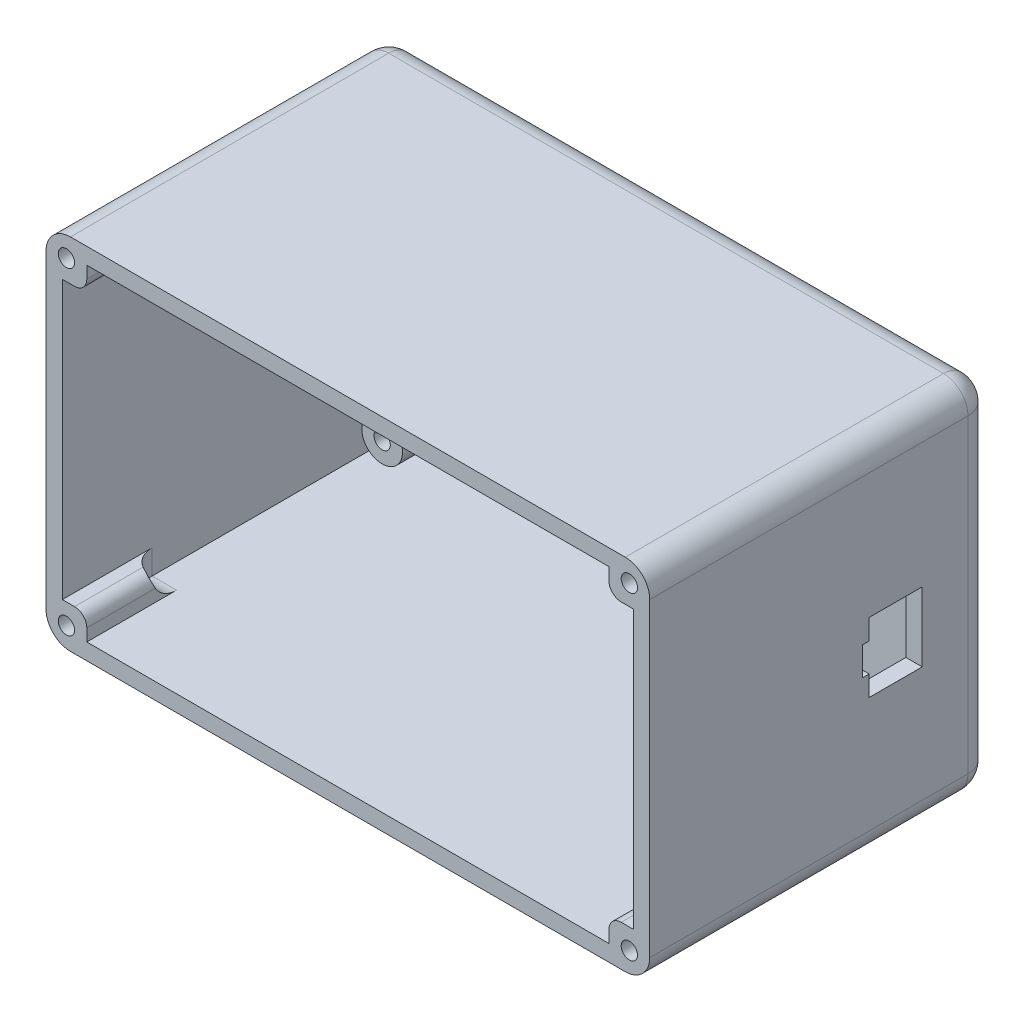
SolidWorks part; units mm, degrees
ref_plane "Front" through (0, 0, 0) normal (0, 0, 1) x (1, 0, 0)
ref_plane "Top" through (0, 0, 0) normal (0, 1, 0) x (1, 0, 0)
ref_plane "Right" through (0, 0, 0) normal (1, 0, 0) x (0, 0, -1)
sketch "Çizim1" plane through (0, 0, 0) normal (0, 0, 1) x (1, 0, 0)
  line L1 (-35, 20) -> (35, 20)
  line L2 (-35, 20) -> (-35, -20)
  line L3 (-35, -20) -> (35, -20)
  line L4 (35, 20) -> (35, -20)
  line L5 (-35, 20) -> (35, -20) construction
  line L6 (-35, -20) -> (35, 20) construction
  point P0 (0, 0)
  dimension "D1" = 70
  dimension "D2" = 40
extrude "Yükseklik-Ekstrüzyon1" add sketch "Çizim1" along normal blind 40
shell "İç Boşaltma2" thickness 2 removed face at (0, 0, 40) outward yes
sketch "Çizim2" plane through (0, 0, 0) normal (0, 0, 1) x (1, 0, 0)
  line L1 (-30.8, 15.5) -> (30.8, 15.5) construction
  line L2 (-30.8, 15.5) -> (-30.8, -15.5) construction
  line L3 (-30.8, -15.5) -> (30.8, -15.5) construction
  line L4 (30.8, 15.5) -> (30.8, -15.5) construction
  line L5 (-30.8, 15.5) -> (30.8, -15.5) construction
  line L6 (-30.8, -15.5) -> (30.8, 15.5) construction
  circle A0 centre (-30.8, 15.5) radius 2.5
  circle A1 centre (-30.8, -15.5) radius 2.5
  circle A2 centre (30.8, -15.5) radius 2.5
  circle A3 centre (30.8, 15.5) radius 2.5
  circle A4 centre (-30.8, 15.5) radius 1
  circle A5 centre (-30.8, -15.5) radius 1
  circle A6 centre (30.8, -15.5) radius 1
  circle A7 centre (30.8, 15.5) radius 1
  point P0 (0, 0)
  dimension "D1" = 5
  dimension "D4" = 2
  dimension "D2" = 61.6
  dimension "D3" = 31
extrude "Yükseklik-Ekstrüzyon2" add sketch "Çizim2" along normal blind 5
fillet "Radyus2" radius 3 8 edges at (0, 22, -2) (-37, 0, -2) (0, -22, -2) (37, 0, -2) (-37, 22, 19) (-37, -22, 19) (37, -22, 19) (37, 22, 19)
sketch "Çizim3" plane through (-37, 0, 0) normal (-1, 0, 0) x (0, 0, 1)
  line L0 (5, 13) -> (5, 18) construction
  line L1 (6.6, 3.36) -> (13.1, 3.36)
  line L2 (6.6, 3.36) -> (6.6, -5.14)
  line L3 (6.6, -5.14) -> (13.1, -5.14)
  line L4 (13.1, 3.36) -> (13.1, 0.86)
  line L5 (40, -22) -> (1, -22) construction
  line L6 (13.1, 0.86) -> (13.9, 0.86)
  line L7 (13.9, 0.86) -> (13.9, -2.64)
  line L8 (13.9, -2.64) -> (13.1, -2.64)
  line L9 (13.1, -2.64) -> (13.1, -5.14)
  dimension "D1" = 1.6
  dimension "D2" = 6.5
  dimension "D3" = 8.5
  dimension "D4" = 16.86
  dimension "D5" = 3.5
  dimension "D6" = 0.8
  dimension "D7" = 2.5
extrude "Kes-Ekstrüzyon1" cut sketch "Çizim3" against normal blind 5
sketch "Çizim4" plane through (37, 0, 0) normal (1, 0, 0) x (0, 0, -1)
  line L8 (-13.1, -2.34) -> (-13.9, -2.34)
  line L9 (-13.1, -4.84) -> (-6.6, -4.84)
  line L10 (-13.1, -4.84) -> (-13.1, -2.34)
  line L11 (-13.1, 3.66) -> (-6.6, 3.66)
  line L12 (-6.6, -4.84) -> (-6.6, 3.66)
  line L13 (-13.9, -2.34) -> (-13.9, 1.16)
  line L14 (-13.9, 1.16) -> (-13.1, 1.16)
  line L15 (-13.1, 1.16) -> (-13.1, 3.66)
  line L16 (-5, 18) -> (-5, 13) construction
  line L17 (-40, 22) -> (-1, 22) construction
  dimension "D2" = 1.6
  dimension "D3" = 18.34
  dimension "D6" = 8.5
  dimension "D7" = 6.5
  dimension "D8" = 2.5
  dimension "D9" = 3.5
  dimension "D10" = 0.8
extrude "Kes-Ekstrüzyon2" cut sketch "Çizim4" against normal blind 5
sketch "Çizim5" plane through (0, 0, 40) normal (0, 0, 1) x (1, 0, 0)
  line L0 (35, 20) -> (-35, 20) construction
  line L1 (-35, 20) -> (-32, 20)
  line L2 (-35, 20) -> (-35, 17)
  line L3 (-35, 17) -> (-32, 17)
  line L4 (-32, 20) -> (-32, 17)
  line L5 (-35, -20) -> (-32, -20)
  line L6 (-35, -20) -> (-35, -17)
  line L7 (-35, -17) -> (-32, -17)
  line L8 (-32, -20) -> (-32, -17)
  line L9 (35, 20) -> (32, 20)
  line L10 (35, 20) -> (35, 17)
  line L11 (35, 17) -> (32, 17)
  line L12 (32, 20) -> (32, 17)
  line L13 (35, -20) -> (32, -20)
  line L14 (35, -20) -> (35, -17)
  line L15 (35, -17) -> (32, -17)
  line L16 (32, -20) -> (32, -17)
  point P18 (-22.1763, 20)
  point P19 (-35, 20)
  point P21 (35, 20)
  point P23 (35, -20)
  point P25 (-35, -20)
  dimension "D1" = 3
extrude "Yükseklik-Ekstrüzyon3" add sketch "Çizim5" against normal blind 8
fillet "Radyus3" radius 3 8 edges at (33.5, 20, 32) (35, 18.5, 32) (33.5, -20, 32) (35, -18.5, 32) (-35, -18.5, 32) (-33.5, -20, 32) (-33.5, 20, 32) (-35, 18.5, 32)
sketch "Çizim6" plane through (0, 0, 40) normal (0, 0, 1) x (1, 0, 0)
  line L0 (37, -19) -> (37, 19) construction
  line L1 (-34.5, 19.5) -> (34.5, 19.5) construction
  line L2 (-34.5, 19.5) -> (-34.5, -19.5) construction
  line L3 (-34.5, -19.5) -> (34.5, -19.5) construction
  line L4 (34.5, 19.5) -> (34.5, -19.5) construction
  line L5 (-34.5, 19.5) -> (34.5, -19.5) construction
  line L6 (-34.5, -19.5) -> (34.5, 19.5) construction
  line L7 (34, 22) -> (-34, 22) construction
  circle A0 centre (-34.5, 19.5) radius 1
  circle A1 centre (-34.5, -19.5) radius 1
  circle A2 centre (34.5, -19.5) radius 1
  circle A3 centre (34.5, 19.5) radius 1
  point P0 (0, 0)
  dimension "D3" = 2
  dimension "D1" = 2.5
  dimension "D2" = 2.5
extrude "Kes-Ekstrüzyon3" cut sketch "Çizim6" against normal blind 8
fillet "Radyus4" radius 1.5 4 edges at (-32, -17, 36) (32, -17, 36) (32, 17, 36) (-32, 17, 36)
